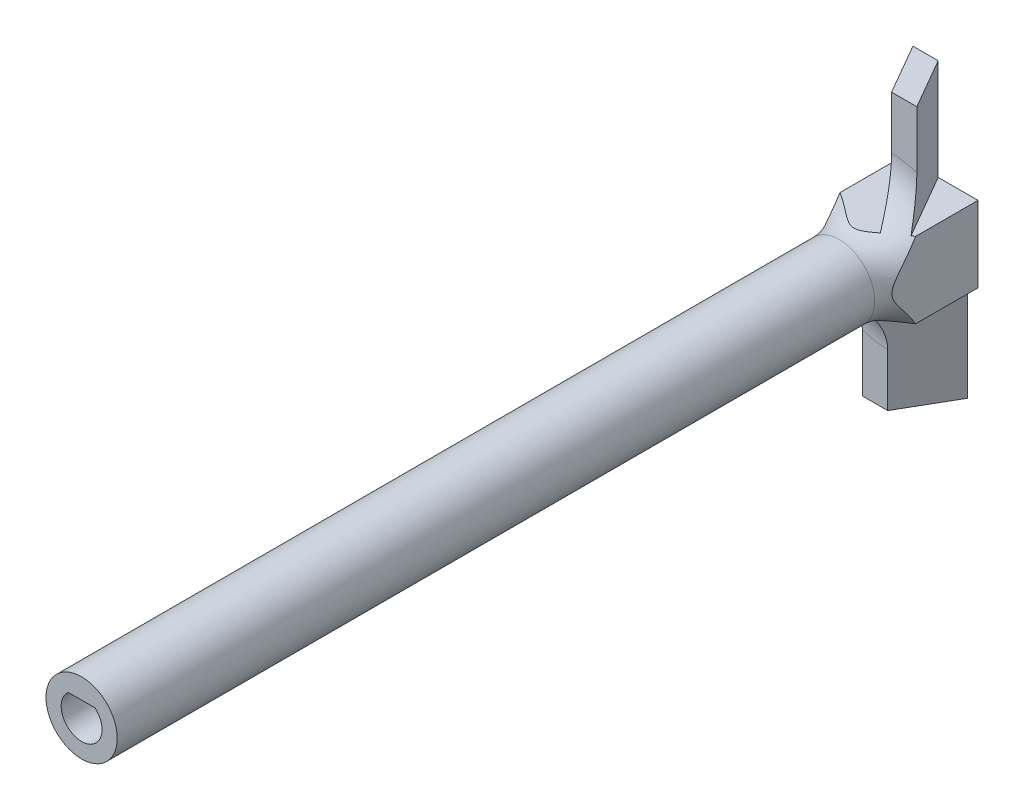
SolidWorks part; units mm, degrees
ref_plane "Front Plane" through (0, 0, 0) normal (0, 0, 1) x (1, 0, 0)
ref_plane "Top Plane" through (0, 0, 0) normal (0, 1, 0) x (1, 0, 0)
ref_plane "Right Plane" through (0, 0, 0) normal (1, 0, 0) x (0, 0, -1)
sketch "Sketch1" plane through (0, 0, 0) normal (0, 0, 1) x (1, 0, 0)
  circle A0 centre (0, 0) radius 4.05
  circle A1 centre (0, 0) radius 7.05
  dimension "D1" = 8.1
  dimension "D2" = 3
extrude "Boss-Extrude1" add sketch "Sketch1" along normal blind 160 contours A0 | A1 A0 region at (0, 0, 0) region at (-6.8506, 0, 0)
sketch "Sketch2" plane through (0, 0, 0) normal (0, 0, -1) x (-1, 0, 0)
  line L0 (-2.6646, 3.05) -> (2.6646, 3.05)
  arc A0 (-2.6646, 3.05) -> (2.6646, 3.05) centre (0, 0) ccw
  circle A1 centre (0, 0) radius 4.05 construction
  point P7 (0, -4.05)
  dimension "D1" = 7.1
sketch "Sketch3" plane through (0, 0, 0) normal (0, 0, -1) x (-1, 0, 0)
  line L1 (-7.5, 7.5) -> (7.5, 7.5)
  line L2 (-7.5, 7.5) -> (-7.5, -7.5)
  line L3 (-7.5, -7.5) -> (7.5, -7.5)
  line L4 (7.5, 7.5) -> (7.5, -7.5)
  line L5 (-7.5, 7.5) -> (7.5, -7.5) construction
  line L6 (-7.5, -7.5) -> (7.5, 7.5) construction
  point P0 (0, 0)
  dimension "D1" = 15
extrude "Boss-Extrude2" add sketch "Sketch3" along normal blind 10
sketch "Sketch4" plane through (0, 7.5, 0) normal (0, 1, 0) x (1, 0, 0)
  line L0 (-0.3868, 10) -> (5.3868, 0)
  line L1 (-7.5, 10) -> (7.5, 10) construction
  line L2 (-7.05, 0) -> (7.05, 0) construction
  line L3 (-5.3868, 10) -> (0.3868, 0)
  line L4 (-4.05, 0) -> (4.05, 0) construction
  line L5 (5.3868, 0) -> (0.3868, 0)
  line L6 (-0.3868, 10) -> (-5.3868, 10)
  line L7 (2.8868, 0) -> (-2.8868, 10) construction
  line L8 (-7.5, 10) -> (-7.5, 0) construction
  point P12 (0, 5)
  dimension "D1" = 60
  dimension "D2" = 5
extrude "Boss-Extrude3" add sketch "Sketch4" along normal blind 20
pattern_circular "CirPattern1" count 2 over 360 about axis through (0, 0, 160) along (0, 0, -1) of "Boss-Extrude3"
fillet "Fillet1" radius 10 1 edges at (7.05, 0, 0)
sketch "Sketch5" plane through (0, 0, 160) normal (0, 0, 1) x (1, 0, 0)
  line L0 (2.6646, 3.05) -> (-2.6646, 3.05) construction
  line L1 (2.6646, 3.05) -> (-2.6646, 3.05)
  circle A0 centre (0, 0) radius 4.05 construction
  arc A1 (-2.6646, 3.05) -> (2.6646, 3.05) centre (0, 0) ccw
extrude "Cut-Extrude2" cut sketch "Sketch5" against normal blind 40
sketch "Sketch6" plane through (0, 0, -10) normal (0, 0, -1) x (-1, 0, 0)
  circle A0 centre (0, 0) radius 2
  dimension "D1" = 4
extrude "Cut-Extrude3" cut sketch "Sketch6" against normal through all
sketch "Sketch7" plane through (0, 0, -10) normal (0, 0, -1) x (-1, 0, 0)
  circle A0 centre (0, 0) radius 3.75
  dimension "D1" = 7.5
extrude "Cut-Extrude4" cut sketch "Sketch7" against normal blind 4
